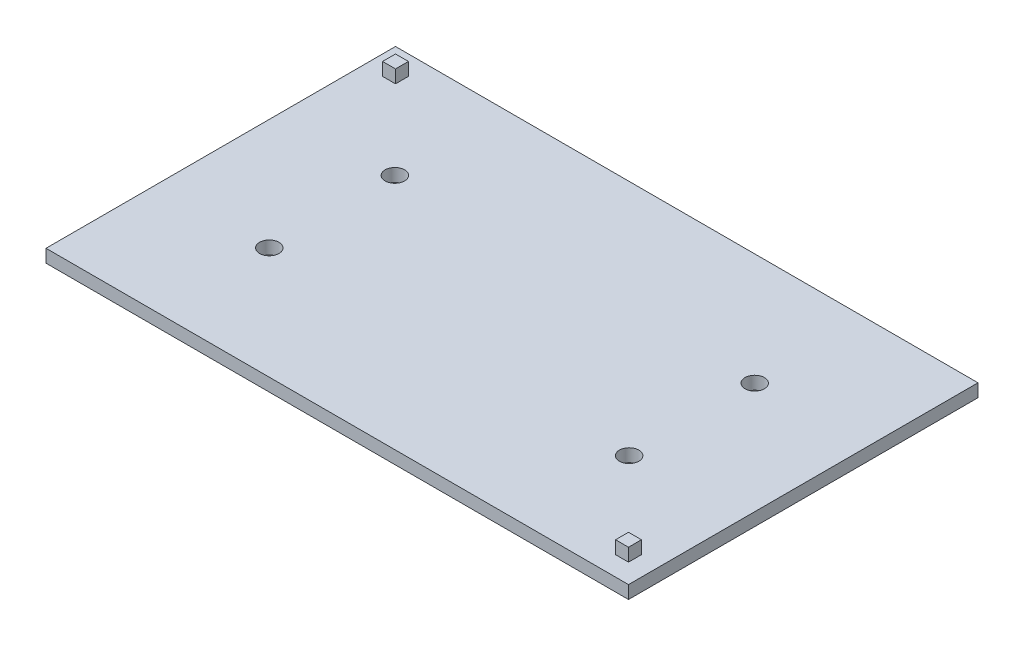
SolidWorks part; units mm, degrees
ref_plane "Front Plane" through (0, 0, 0) normal (0, 0, 1) x (1, 0, 0)
ref_plane "Top Plane" through (0, 0, 0) normal (0, 1, 0) x (1, 0, 0)
ref_plane "Right Plane" through (0, 0, 0) normal (1, 0, 0) x (0, 0, -1)
ref_plane "Plane1" through (0, 1, 0) normal (0, 1, 0) x (1, 0, 0)
sketch "Sketch2" plane through (0, 1, 0) normal (0, 1, 0) x (1, 0, 0)
  line L0 (-45, 0) -> (45, 0) construction
  line L1 (-45, 24) -> (45, 24)
  line L2 (0, 27) -> (0, -27) construction
  line L3 (-45, 27) -> (45, 27)
  line L4 (-45, 27) -> (-45, -27)
  line L5 (-45, -27) -> (45, -27)
  line L6 (45, 27) -> (45, -27)
  line L7 (-45, -24) -> (45, -24)
  line L8 (-42, 27) -> (-42, -27)
  line L9 (42, 27) -> (42, -27)
  line L13 (-42, 22) -> (-40, 22)
  line L14 (-40, 24) -> (-40, 22)
  line L17 (42, -22) -> (40, -22)
  line L18 (40, -24) -> (40, -22)
  line L21 (-42, -22) -> (-40, -22)
  line L22 (-40, -24) -> (-40, -22)
  line L25 (42, 22) -> (40, 22)
  line L26 (40, 24) -> (40, 22)
  circle A0 centre (-27.8, 9.7) radius 1.5
  circle A1 centre (-27.8, -9.7) radius 1.5
  circle A2 centre (27.8, -9.7) radius 1.5
  circle A4 centre (-27.8, 9.7) radius 3
  circle A5 centre (-27.8, -9.7) radius 3
  circle A6 centre (27.8, -9.7) radius 3
  circle A7 centre (27.8, 9.7) radius 1.5
  circle A8 centre (27.8, 9.7) radius 3
  point P10 (0, 0)
  point P28 (0, 0)
  point P33 (0, 0)
  point P37 (0, 0)
  point P41 (0, 0)
  point P46 (0, 0)
  point P47 (-67.3076, 9.6982)
  point P48 (0, 0)
  point P49 (-40, 24)
  point P50 (-42, 22)
  point P51 (-39.9986, -24)
  point P52 (-42, 22)
  point P53 (41.4594, -22)
  point P54 (42, -22)
  point P55 (0, 0)
  dimension "D11" = 2
  dimension "D16" = 6
  dimension "D17" = 6
  dimension "D18" = 6
  dimension "D19" = 6
  dimension "D20" = 3
  dimension "D21" = 3
  dimension "D22" = 3
  dimension "D23" = 3
  dimension "D1" = 90
  dimension "D2" = 54
  dimension "D3" = 9.7
  dimension "D4" = 19.4
  dimension "D5" = 27.8
  dimension "D6" = 55.6
  dimension "D7" = 3
  dimension "D8" = 3
  dimension "D9" = 3
  dimension "D10" = 3
  dimension "D12" = 2
  dimension "D13" = 2
  dimension "D14" = 2
  dimension "D15" = 9.7
extrude "Boss-Extrude1" add sketch "Sketch2" along normal blind 2 separate body contours A0 | A1 | L4 L3 L6 L5 | A2 | A7
extrude "Boss-Extrude3" add sketch "Sketch2<4>" along normal blind 4 contours L18 L7 L9 L17 | L14 L1 L8 L13
sketch "Sketch2<4>" plane through (0, 1, 0) normal (0, 1, 0) x (1, 0, 0) same geometry as "Sketch2"
